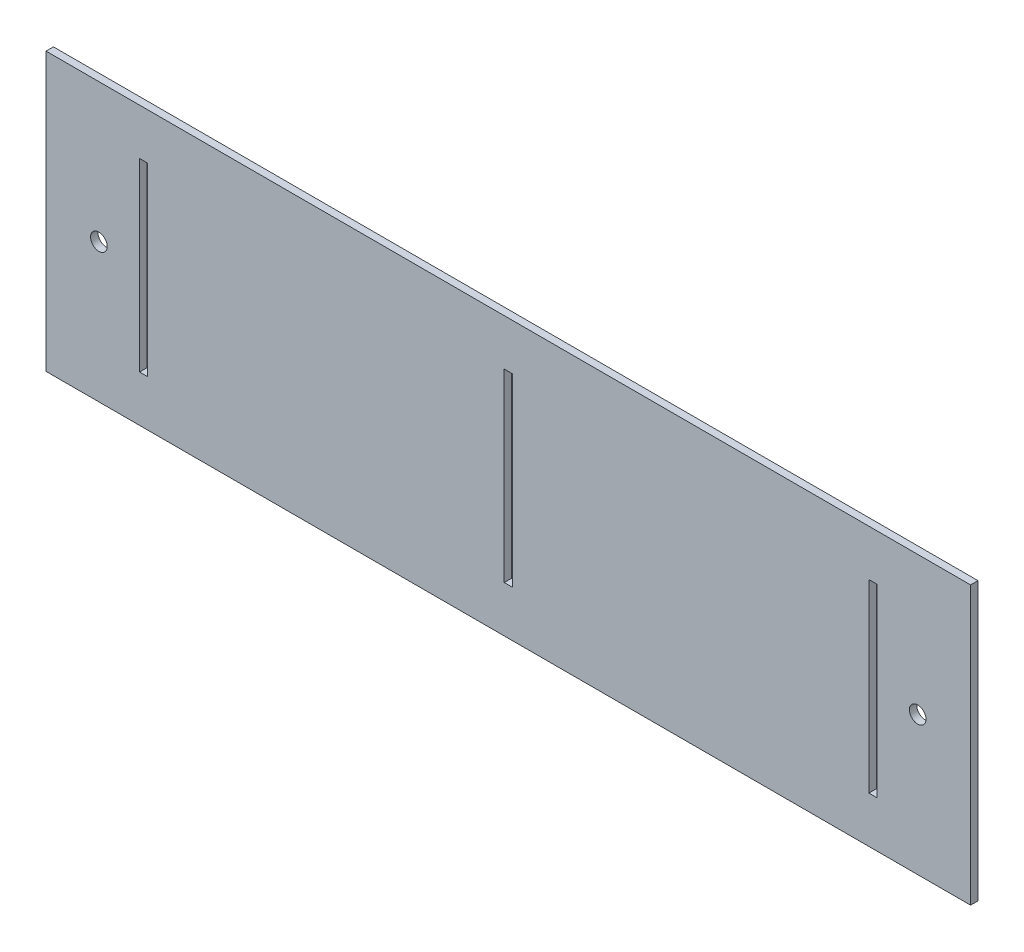
SolidWorks part; units mm, degrees
ref_plane "前视基准面" through (0, 0, 0) normal (0, 0, 1) x (1, 0, 0)
ref_plane "上视基准面" through (0, 0, 0) normal (0, 1, 0) x (1, 0, 0)
ref_plane "右视基准面" through (0, 0, 0) normal (1, 0, 0) x (0, 0, -1)
sketch "草图2" plane through (0, 0, 0) normal (0, 0, 1) x (1, 0, 0)
  line L1 (-73.6818, 78.3847) -> (176.3182, 78.3847)
  line L2 (-73.6818, 78.3847) -> (-73.6818, 3.3847)
  line L3 (-73.6818, 3.3847) -> (176.3182, 3.3847)
  line L4 (176.3182, 78.3847) -> (176.3182, 3.3847)
  dimension "D1" = 250
  dimension "D2" = 75
sketch "草图4" plane through (0, 0, 0) normal (0, 0, 1) x (1, 0, 0)
  line L5 (-73.6818, 78.3847) -> (176.3182, 78.3847) construction
  line L6 (-73.6818, 78.3847) -> (-73.6818, 3.3847) construction
  line L7 (51.3182, 96.8277) -> (51.3182, 60.5853) construction
  line L8 (151.0182, 40.8847) -> (148.8182, 40.8847) construction
  line L9 (149.9182, 15.8847) -> (149.9182, 65.8847) construction
  line L10 (148.8182, 65.8847) -> (148.8182, 15.8847)
  line L11 (-48.3818, 65.8847) -> (-46.1818, 65.8847)
  line L12 (-48.3818, 65.8847) -> (-48.3818, 15.8847)
  line L13 (-48.3818, 15.8847) -> (-46.1818, 15.8847)
  line L14 (-46.1818, 65.8847) -> (-46.1818, 15.8847)
  line L15 (-47.2818, 15.8847) -> (-47.2818, 65.8847) construction
  line L16 (-48.3818, 40.8847) -> (-46.1818, 40.8847) construction
  line L17 (50.2182, 65.8847) -> (52.4182, 65.8847)
  line L18 (50.2182, 65.8847) -> (50.2182, 15.8847)
  line L19 (50.2182, 15.8847) -> (52.4182, 15.8847)
  line L20 (52.4182, 65.8847) -> (52.4182, 15.8847)
  line L21 (51.3182, 15.8847) -> (51.3182, 65.8847) construction
  line L22 (50.2182, 40.8847) -> (52.4182, 40.8847) construction
  line L26 (151.0182, 15.8847) -> (148.8182, 15.8847)
  line L27 (151.0182, 65.8847) -> (151.0182, 15.8847)
  line L28 (151.0182, 65.8847) -> (148.8182, 65.8847)
  line L29 (-73.6818, 3.3847) -> (176.3182, 3.3847) construction
  point P0 (51.3182, 78.3847)
  point P24 (51.3182, 40.8847)
  point P29 (-47.2818, 40.8847)
  point P34 (51.3182, 40.8847)
  point P35 (149.9182, 40.8847)
  dimension "D2" = 50
  dimension "D3" = 2.2
  dimension "D4" = 50
  dimension "D5" = 26.4
  dimension "D8" = 37.5
extrude "凸台-拉伸3" add sketch "草图2" along normal blind 2
extrude "切除-拉伸1" cut sketch "草图4" against normal blind 2 and the other way blind 2
sketch "草图5" plane through (0, 0, 0) normal (0, 0, 1) x (1, 0, 0)
  line L0 (-73.6818, 78.3847) -> (-73.6818, 3.3847) construction
  line L1 (-73.6818, 78.3847) -> (176.3182, 78.3847) construction
  line L2 (-73.6818, 3.3847) -> (176.3182, 3.3847) construction
  line L3 (51.3182, 78.3847) -> (51.3182, 2.8269) construction
  line L4 (-48.3818, 65.8847) -> (-48.3818, 15.8847) construction
  circle A0 centre (-59.3818, 40.8847) radius 2.25
  circle A1 centre (162.0182, 40.8847) radius 2.25
  point P0 (-73.6818, 40.8847)
  point P1 (51.3182, 78.3847)
  point P4 (51.3182, 3.3847)
  point P13 (0, 0)
  dimension "D1" = 4.5
  dimension "D2" = 11
extrude "切除-拉伸2" cut sketch "草图5" against normal blind 10 and the other way blind 2
